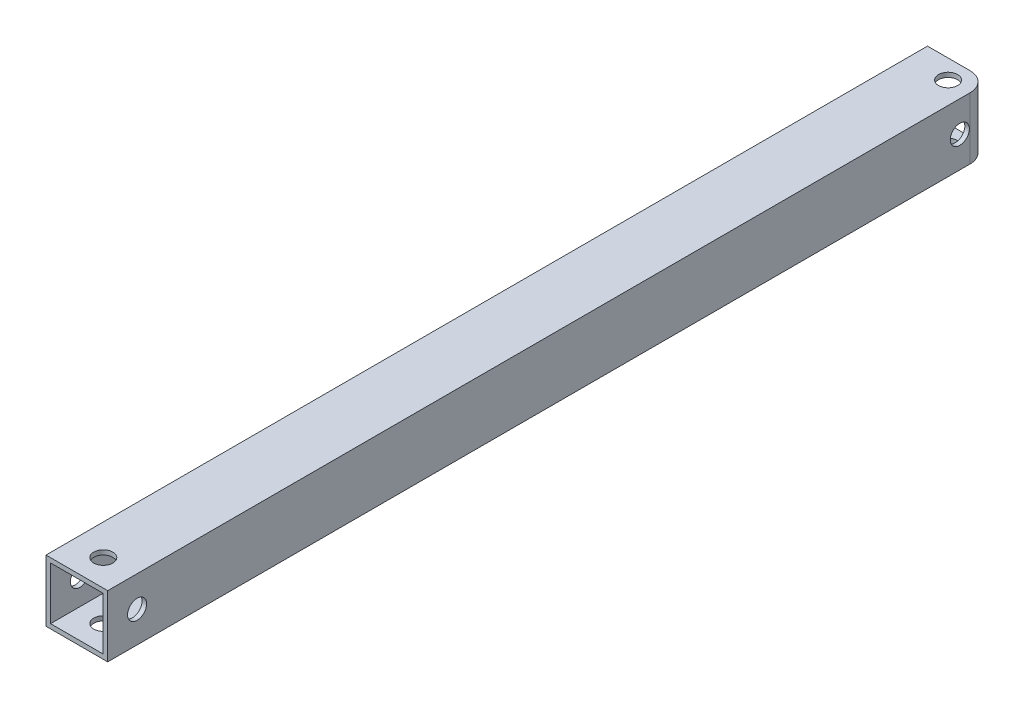
SolidWorks part; units mm, degrees
material "AISI 1020 Acero laminado en frío"
ref_plane "Alzado" through (0, 0, 0) normal (0, 0, 1) x (1, 0, 0)
ref_plane "Planta" through (0, 0, 0) normal (0, 1, 0) x (1, 0, 0)
ref_plane "Vista lateral" through (0, 0, 0) normal (1, 0, 0) x (0, 0, -1)
sketch "Croquis1" plane through (0, 0, 0) normal (0, 0, 1) x (1, 0, 0)
  line L1 (21, -21) -> (-21, -21)
  line L2 (21, -21) -> (21, 21)
  line L3 (21, 21) -> (-21, 21)
  line L4 (-21, -21) -> (-21, 21)
  line L5 (21, -21) -> (-21, 21) construction
  line L6 (21, 21) -> (-21, -21) construction
  point P0 (0, 0)
  point P6 (-21, 0)
  dimension "D1" = 42
  dimension "D2" = 42
extrude "Saliente-Extruir1" add sketch "Croquis1" along normal mid plane 600
sketch3d "Croquis3D1"
  line L0 (-17.9, -17.9, 300) -> (17.9, -17.9, 300)
  line L1 (17.9, -17.9, 300) -> (17.9, 17.9, 300)
  line L2 (17.9, 17.9, 300) -> (-17.9, 17.9, 300)
  line L3 (-17.9, 17.9, 300) -> (-17.9, -17.9, 300)
  line L4 (-17.9, -17.9, 300) -> (17.9, -17.9, 300)
  line L5 (17.9, -17.9, 300) -> (17.9, 17.9, 300)
  line L6 (17.9, 17.9, 300) -> (-17.9, 17.9, 300)
  line L7 (-17.9, 17.9, 300) -> (-17.9, -17.9, 300)
  dimension "D1" = 3.1
extrude "Cortar-Extruir1" cut sketch "Croquis3D1" along direction (0, 0, 1) on the side against the normal through all
sketch "Croquis2" plane through (-21, 0, 0) normal (-1, 0, 0) x (0, 0, 1)
  line L1 (300, -17.9) -> (-300, -17.9)
  line L2 (300, -17.9) -> (300, 17.9)
  line L3 (300, 17.9) -> (-300, 17.9)
  line L4 (-300, 21) -> (-300, -21)
  line L5 (-300, -21) -> (300, -21)
  line L6 (300, -21) -> (300, 21)
  line L7 (300, 21) -> (-300, 21)
  line L8 (-300, 21) -> (-300, -21)
  line L9 (-300, -21) -> (300, -21)
  line L10 (300, -21) -> (300, 21)
  line L11 (300, 21) -> (-300, 21)
  line L12 (-300, -17.9) -> (-300, 17.9)
  line L13 (300, -17.9) -> (-300, 17.9) construction
  line L14 (300, 17.9) -> (-300, -17.9) construction
  point P2 (0, 0)
  dimension "D2" = 3.1
  dimension "D1" = 0
sketch "Croquis3" plane through (0, -21, 0) normal (0, -1, 0) x (1, 0, 0)
  line L0 (-21, 300) -> (21, 300) construction
  line L1 (0, 166.4406) -> (0, -46.6838) construction
  circle A0 centre (0, 282) radius 6.5
  dimension "D1" = 13
  dimension "D2" = 18
extrude "Cortar-Extruir3" cut sketch "Croquis3" against normal blind 60 contours A0
sketch "Croquis4" plane through (21, 0, 0) normal (1, 0, 0) x (0, 0, -1)
  line L0 (280, 42.844) -> (280, -60.1919) construction
  line L1 (180.7653, 0) -> (-212.4531, 0) construction
  line L2 (300, 21) -> (300, -21) construction
  circle A0 centre (280, 0) radius 6.5
  dimension "D1" = 13
  dimension "D2" = 20
extrude "Cortar-Extruir4" cut sketch "Croquis4" against normal blind 70
sketch "Croquis5" plane through (0, 21, 0) normal (0, 1, 0) x (1, 0, 0)
  line L0 (0, 173.2825) -> (0, -26.5385) construction
  line L1 (21, 300) -> (-21, 300) construction
  line L2 (6, 163.2061) -> (6, 116.6333) construction
  circle A0 centre (6, 287) radius 6.5
  dimension "D1" = 13
  dimension "D2" = 13
  dimension "D3" = 6
extrude "Cortar-Extruir5" cut sketch "Croquis5" against normal through all
fillet "Redondeo1" radius 13 1 edges at (21, 0, -300)
sketch "Croquis6" plane through (-21, 0, 0) normal (-1, 0, 0) x (0, 0, 1)
  line L0 (168.557, 0) -> (114.2629, 0) construction
  line L1 (300, 21) -> (300, -21) construction
  circle A0 centre (280, 0) radius 6.5
  dimension "D2" = 13
  dimension "D1" = 20
extrude "Cortar-Extruir6" cut sketch "Croquis6" against normal blind 60
